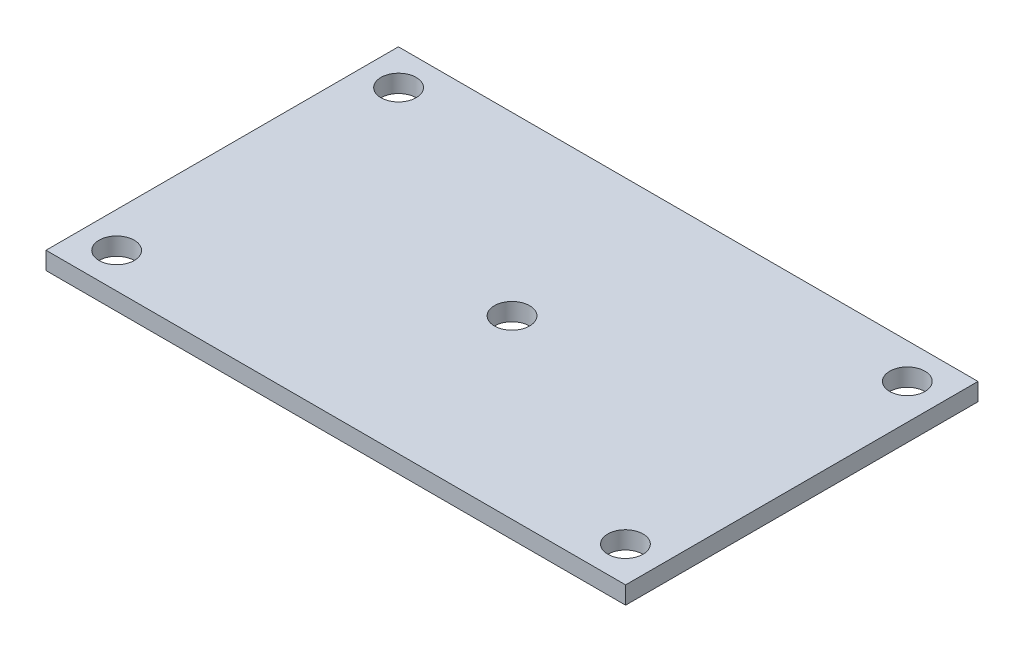
SolidWorks part; units mm, degrees
ref_plane "Plan de face" through (0, 0, 0) normal (0, 0, 1) x (1, 0, 0)
ref_plane "Plan de dessus" through (0, 0, 0) normal (0, 1, 0) x (1, 0, 0)
ref_plane "Plan de droite" through (0, 0, 0) normal (1, 0, 0) x (0, 0, -1)
sketch "Esquisse1" plane through (0, 0, 0) normal (0, 1, 0) x (1, 0, 0)
  line L0 (-72.19, 40) -> (-72.19, -40) construction
  line L1 (-90.2375, -50) -> (90.2375, -50)
  line L2 (-90.2375, -50) -> (-90.2375, 50)
  line L3 (-90.2375, 50) -> (90.2375, 50)
  line L4 (90.2375, -50) -> (90.2375, 50)
  line L5 (-90.2375, -50) -> (90.2375, 50) construction
  line L6 (-90.2375, 50) -> (90.2375, -50) construction
  line L7 (-72.19, 40) -> (72.19, 40) construction
  line L8 (0, 0) -> (-104.2, 0) construction
  line L9 (0, 0) -> (0, 50) construction
  circle A0 centre (-72.19, 40) radius 5
  circle A1 centre (72.19, 40) radius 5
  circle A2 centre (72.19, -40) radius 5
  circle A3 centre (-72.19, -40) radius 5
  circle A4 centre (0, 0) radius 5
  point P0 (0, 0)
  dimension "D4" = 10
  dimension "D5" = 10
  dimension "D1" = 100
  dimension "D2" = 80
  dimension "D3" = 144.38
extrude "Boss.-Extru.1" add sketch "Esquisse1" along normal blind 5
sketch "Esquisse2" plane through (0, 5, 0) normal (0, 1, 0) x (1, 0, 0)
  line L0 (-90.2375, -50) -> (90.2375, -50) construction
  line L1 (-90.2375, 50) -> (-82.2375, 50)
  line L2 (-90.2375, 50) -> (-90.2375, -50)
  line L3 (-90.2375, -50) -> (-82.2375, -50)
  line L4 (-82.2375, 50) -> (-82.2375, -50)
  line L5 (0, 0) -> (0, 50) construction
  line L6 (90.2375, 50) -> (-90.2375, 50) construction
  line L7 (82.2375, 50) -> (82.2375, -50)
  line L8 (90.2375, -50) -> (82.2375, -50)
  line L9 (90.2375, 50) -> (90.2375, -50)
  line L10 (90.2375, 50) -> (82.2375, 50)
  dimension "D1" = 8
extrude "Enlèv. mat.-Extru.1" cut sketch "Esquisse2" against normal up to surface (5 mm away) up to face at (-72.19, 0, 35)
